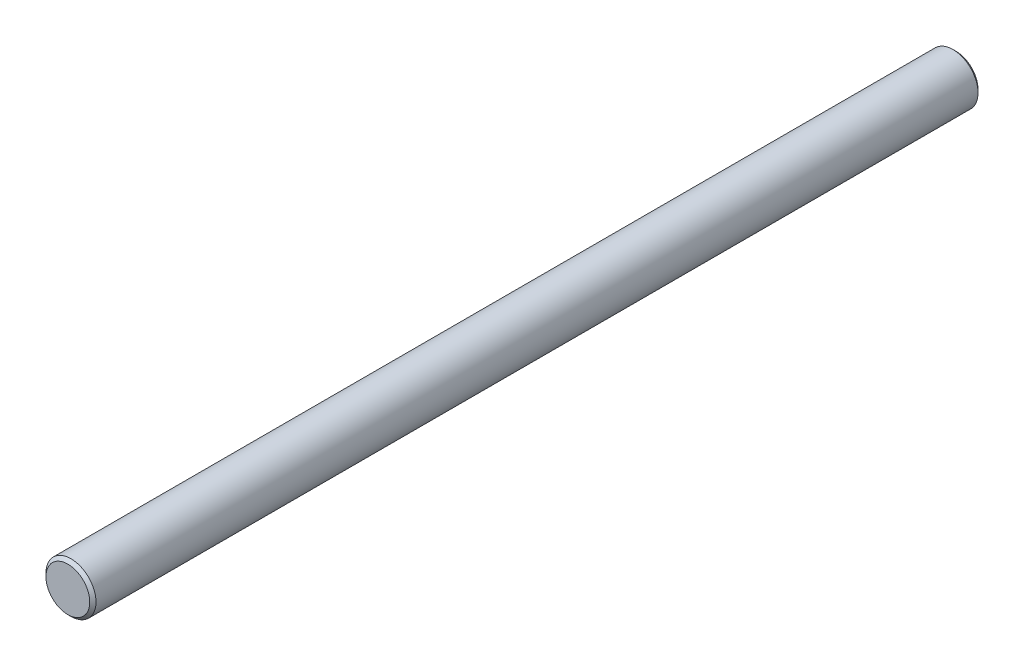
SolidWorks part; units mm, degrees
ref_plane "Front Plane" through (0, 0, 0) normal (0, 0, 1) x (1, 0, 0)
ref_plane "Top Plane" through (0, 0, 0) normal (0, 1, 0) x (1, 0, 0)
ref_plane "Right Plane" through (0, 0, 0) normal (1, 0, 0) x (0, 0, -1)
sketch "Sketch1" plane through (0, 0, 0) normal (0, 0, 1) x (1, 0, 0)
  circle A0 centre (0, 0) radius 4
  dimension "D1" = 8
extrude "Boss-Extrude1" add sketch "Sketch1" along normal mid plane 142 contours A0
chamfer "Chamfer1" distance 0.5 angle 45 2 edges at (4, 0, -71) (4, 0, 71)
